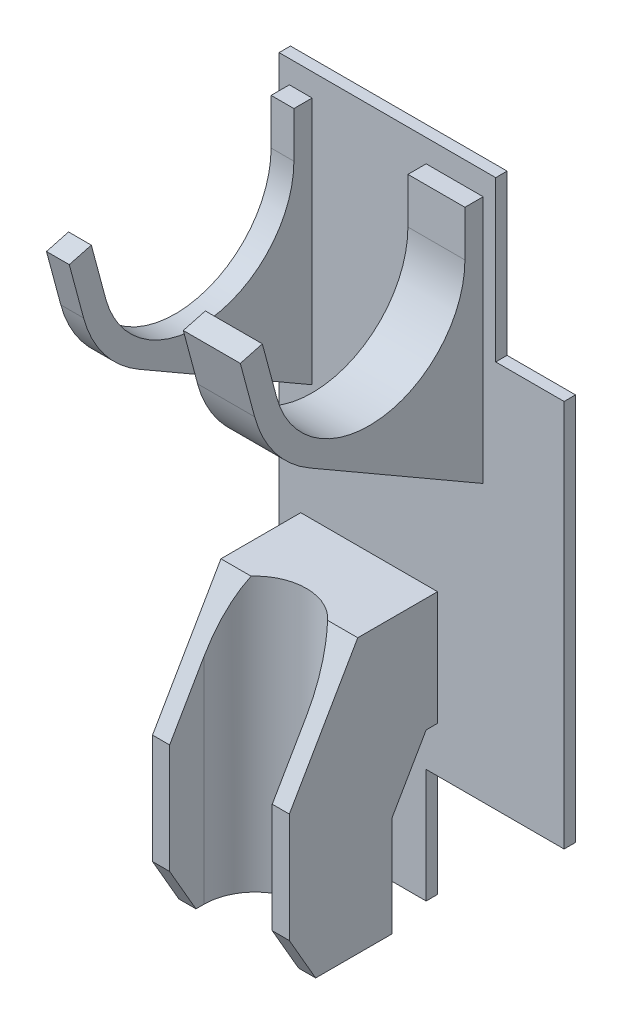
SolidWorks part; units mm, degrees
ref_plane "Front Plane" through (0, 0, 0) normal (0, 0, 1) x (1, 0, 0)
ref_plane "Top Plane" through (0, 0, 0) normal (0, 1, 0) x (1, 0, 0)
ref_plane "Right Plane" through (0, 0, 0) normal (1, 0, 0) x (0, 0, -1)
sketch "Sketch1" plane through (0, 0, 0) normal (0, 0, 1) x (1, 0, 0)
  line L0 (0, 0) -> (20.4338, 0) construction
  line L1 (0, 0) -> (0, 12.1018) construction
  line L2 (20, -250) -> (-20, -250) construction
  line L3 (-39.5, 70) -> (55.5, 70)
  line L4 (-39.5, 70) -> (-39.5, -170)
  line L5 (-39.5, -170) -> (85.5, -170)
  line L6 (85.5, 0) -> (85.5, -170)
  line L7 (-34.5, 75) -> (-34.5, 5) construction
  line L8 (50.5, 3.8197) -> (50.5, 76.1803) construction
  line L9 (40.5, 80) -> (-29.5, 80) construction
  line L10 (55.5, 70) -> (55.5, 0)
  line L11 (55.5, 0) -> (85.5, 0)
  dimension "D1" = 80
  dimension "D2" = 5
  dimension "D3" = 30
  dimension "D4" = 10
  dimension "D5" = 240
  dimension "D6" = 125
  dimension "D7" = 5
ref_plane "Plane1" through (0, 0, -40) normal (0, 0, -1) x (-1, 0, 0)
sketch "Sketch2" plane through (0, 0, -40) normal (0, 0, -1) x (-1, 0, 0)
  line L0 (39.5, -170) -> (-85.5, -170) construction
  line L1 (39.5, 70) -> (39.5, -170) construction
  line L2 (39.5, 70) -> (-55.5, 70) construction
  line L3 (-55.5, 70) -> (-55.5, 0) construction
  line L4 (-55.5, 0) -> (-85.5, 0) construction
  line L5 (-85.5, 0) -> (-85.5, -170) construction
  line L6 (39.5, -170) -> (-85.5, -170)
  line L7 (39.5, 70) -> (39.5, -170)
  line L8 (39.5, 70) -> (-55.5, 70)
  line L9 (-55.5, 70) -> (-55.5, 0)
  line L10 (-55.5, 0) -> (-85.5, 0)
  line L11 (-85.5, 0) -> (-85.5, -170)
extrude "Boss-Extrude1" add sketch "Sketch2" along normal blind 5 from offset 10 contours L10 L11 L6 L7 L8 L9 region at (19.4247, -56.3978, -40)
sketch "Sketch3" plane through (0, 0, 0) normal (1, 0, 0) x (0, 0, -1)
  line L0 (42, 40) -> (42, 60)
  line L1 (50, 0) -> (50, -170) construction
  line L2 (-56.5042, 49.9639) -> (-46.8449, 52.5521)
  line L3 (-26, -5.0333) -> (50, -48.9119)
  line L4 (0, 0) -> (-142.9934, 0) construction
  line L5 (0, 40) -> (-98.3531, 66.3536) construction
  line L6 (50, -170) -> (55, -170) construction
  line L7 (55, -170) -> (55, 0) construction
  line L8 (55, 0) -> (50, 0) construction
  line L9 (50, 70) -> (50, 0) construction
  line L10 (50, 0) -> (55, 0) construction
  line L11 (55, 0) -> (55, 70) construction
  line L12 (55, 70) -> (50, 70) construction
  line L13 (50, 0) -> (50, -170) construction
  line L14 (50, -170) -> (55, -170) construction
  line L15 (55, -170) -> (55, 0) construction
  line L16 (55, 0) -> (50, 0) construction
  line L17 (50, 70) -> (50, 0) construction
  line L18 (50, 0) -> (55, 0) construction
  line L19 (55, 0) -> (55, 70) construction
  line L20 (55, 70) -> (50, 70) construction
  line L22 (-46.8449, 52.5521) -> (-40.5689, 29.1296)
  line L23 (-56.5042, 49.9639) -> (-50.2281, 26.5414)
  line L24 (50, -48.9119) -> (55, -48.9119)
  line L25 (55, -48.9119) -> (55, -28.9119)
  line L26 (55, -28.9119) -> (50, -28.9119)
  line L27 (50, -28.9119) -> (50, 30)
  line L28 (50, 30) -> (55, 30)
  line L29 (55, 30) -> (55, 60)
  line L30 (42, 60) -> (55, 60)
  line L31 (55, -100) -> (15, -100)
  line L32 (15, -100) -> (-15, -151.9615)
  line L33 (-15, -151.9615) -> (-15, -200)
  line L34 (-3.453, -220) -> (30, -220)
  line L35 (30, -220) -> (30, -175.9808)
  line L36 (30, -175.9808) -> (45, -150)
  line L37 (45, -150) -> (55, -150)
  line L40 (0, -250) -> (0, 40) construction
  line L42 (50, -110) -> (55, -110)
  line L44 (50, -140) -> (55, -140)
  line L45 (-15, -200) -> (-3.453, -220)
  line L46 (55, 0) -> (55, -170) construction
  line L47 (55, -150) -> (55, -140)
  line L48 (50, -140) -> (50, -110)
  line L49 (55, -100) -> (55, -110)
  line L50 (50, -80) -> (-50, -80)
  line L51 (-50, -80) -> (-50, -245)
  line L52 (-50, -245) -> (50, -245)
  line L53 (50, -245) -> (50, -150)
  line L54 (50, -80) -> (50, -100)
  circle A0 centre (0, 40) radius 40 construction
  circle A1 centre (0, 40) radius 40 construction
  arc A2 (-40.5689, 29.1296) -> (42, 40) centre (0, 40) ccw
  circle A4 centre (0, 40) radius 42 construction
  arc A5 (-50.2281, 26.5414) -> (-26, -5.0333) centre (0, 40) ccw
  point P38 (52.5, -170)
  point P39 (47, -170)
  point P53 (47, -150)
  point P54 (47, -149.8134)
  point P55 (47, -150)
  point P56 (47, -160.2736)
  point P57 (0, 0)
  dimension "D2" = 15
  dimension "D3" = 75
  dimension "D5" = 30
  dimension "D6" = 10
  dimension "D7" = 30
  dimension "D8" = 20
  dimension "D9" = 20
  dimension "D10" = 50
  dimension "D11" = 30
  dimension "D12" = 30
  dimension "D13" = 30
  dimension "D14" = 5
  dimension "D15" = 10
  dimension "D16" = 10
  dimension "D17" = 30
  dimension "D18" = 50
  dimension "D19" = 20
  dimension "D20" = 65
  dimension "D21" = 100
  dimension "D22" = 20
  dimension "D23" = 165
  dimension "D1" = 2
  dimension "D4" = 10
extrude "Boss-Extrude2" add sketch "Sketch3" against normal blind 10 from offset 25 contours L23 A5 L3 L24 L25 L26 L27 L28 L29 L30 L0 A2 L22 L2 region at (0, 0.1262, -17.9978) offset against normal yes
extrude "Boss-Extrude3" add sketch "Sketch3<3>" along normal blind 25 from offset 25 contours L23 A5 L3 L24 L25 L26 L27 L28 L29 L30 L0 A2 L22 L2 region at (0, 0.1262, -17.9978)
sketch "Sketch3<3>" plane through (0, 0, 0) normal (1, 0, 0) x (0, 0, -1) same geometry as "Sketch3"
sketch "Sketch4" plane through (0, 0, 0) normal (0, 1, 0) x (1, 0, 0)
  line L4 (22.5, -15) -> (30, -15)
  line L5 (30, -15) -> (30, 50)
  line L6 (-39.5, 50) -> (55.5, 50) construction
  line L7 (30, 50) -> (25, 50)
  line L8 (-22.5, 0) -> (-22.5, -15)
  line L9 (22.5, 0) -> (22.5, -15)
  line L15 (0, 55) -> (0, 15) construction
  line L16 (0, 0) -> (0, 92.7772) construction
  line L17 (-22.5, -15) -> (-30, -15)
  line L18 (-30, -15) -> (-30, 50)
  line L19 (-25, 50) -> (-25, 55)
  line L20 (-39.5, 55) -> (55.5, 55) construction
  line L21 (-25, 55) -> (25, 55)
  line L22 (25, 55) -> (25, 50)
  line L23 (-25, 50) -> (-30, 50)
  arc A0 (22.5, 0) -> (-22.5, 0) centre (0, 0) ccw
  point P17 (0, 50)
  dimension "D1" = 45
  dimension "D2" = 7.5
  dimension "D3" = 65
  dimension "D4" = 50
extrude "Boss-Extrude6" add sketch "Sketch4" against normal up to vertex (220 mm away) from vertex up to point (0, -220, -30) starting at point (0, -100, -55)
extrude "Cut-Extrude1" cut sketch "Sketch3<8>" against normal through all both and the other way through all contours L54 L50 L51 L52 L53 L37 L36 L35 L34 L45 L33 L32 L31 region at (0, -98.0706, -32.5)
sketch "Sketch3<8>" plane through (0, 0, 0) normal (1, 0, 0) x (0, 0, -1) same geometry as "Sketch3"
